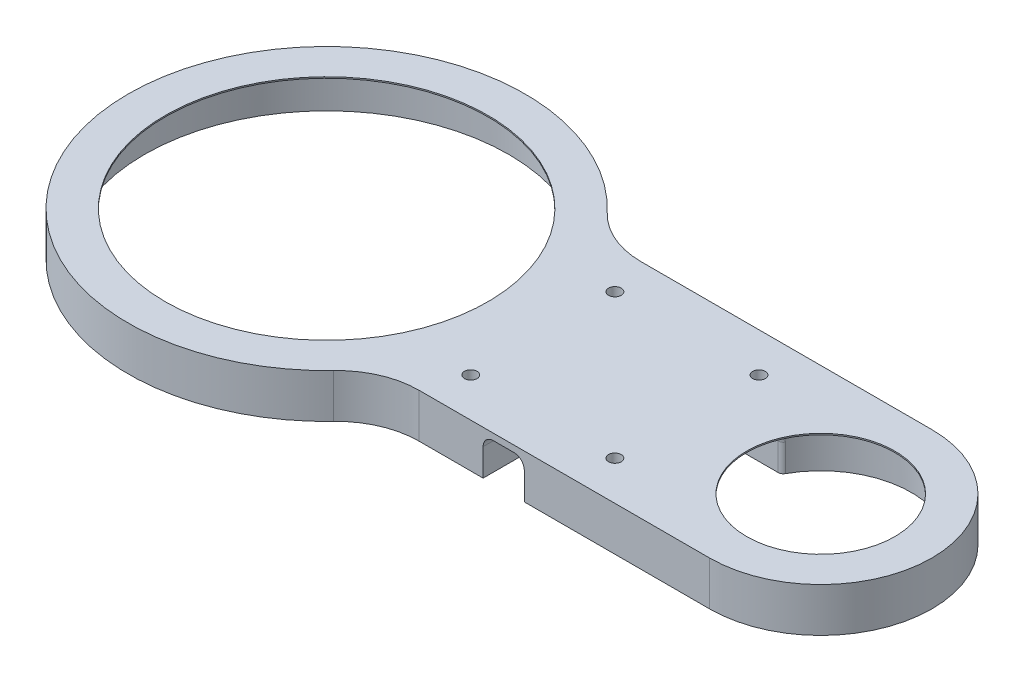
SolidWorks part; units mm, degrees
ref_plane "Front Plane" through (0, 0, 0) normal (0, 0, 1) x (1, 0, 0)
ref_plane "Top Plane" through (0, 0, 0) normal (0, 1, 0) x (1, 0, 0)
ref_plane "Right Plane" through (0, 0, 0) normal (1, 0, 0) x (0, 0, -1)
sketch "Sketch1" plane through (0, 0, 0) normal (0, 1, 0) x (1, 0, 0)
  line L0 (0, 0) -> (76.2, 0) construction
  line L1 (25.3542, -17.145) -> (76.2, -17.145)
  line L2 (25.3542, 17.145) -> (76.2, 17.145)
  circle A0 centre (0, 0) radius 28.067
  circle A1 centre (76.2, 0) radius 13.97
  arc A2 (76.2, 17.145) -> (76.2, -17.145) centre (76.2, 0) cw
  arc A3 (25.3542, 17.145) -> (25.3542, -17.145) centre (0, 0) ccw
  dimension "D1" = 56.134
  dimension "D2" = 27.94
  dimension "D4" = 3.175
  dimension "D5" = 2.54
  dimension "D3" = 76.2
extrude "Boss-Extrude1" add sketch "Sketch1" along normal blind 6.6
fillet "Fillet1" radius 12.7 2 edges at (25.3542, 3.3, -17.145) (25.3542, 3.3, 17.145)
sketch "Sketch2" plane through (0, 6.6, 0) normal (0, 1, 0) x (1, 0, 0)
  line L2 (76.2, 17.145) -> (31.3811, 17.145)
  line L3 (31.3811, -17.145) -> (76.2, -17.145)
  line L4 (76.2, 17.145) -> (31.3811, 17.145)
  line L5 (31.3811, -17.145) -> (76.2, -17.145)
  circle A0 centre (0, 0) radius 24.892
  circle A1 centre (0, 0) radius 28.067 construction
  circle A3 centre (76.2, 0) radius 13.97 construction
  arc A4 (76.2, -17.145) -> (76.2, 17.145) centre (76.2, 0) ccw
  arc A5 (22.1784, 21.0928) -> (31.3811, 17.145) centre (31.3811, 29.845) ccw
  arc A6 (22.1784, 21.0928) -> (22.1784, -21.0928) centre (0, 0) ccw
  arc A7 (31.3811, -17.145) -> (22.1784, -21.0928) centre (31.3811, -29.845) ccw
  arc A8 (76.2, -17.145) -> (76.2, 17.145) centre (76.2, 0) ccw
  arc A9 (22.1784, 21.0928) -> (31.3811, 17.145) centre (31.3811, 29.845) ccw
  arc A10 (22.1784, 21.0928) -> (22.1784, -21.0928) centre (0, 0) ccw
  arc A11 (31.3811, -17.145) -> (22.1784, -21.0928) centre (31.3811, -29.845) ccw
  circle A13 centre (76.2, 0) radius 11.43
  dimension "D2" = 3.175
  dimension "D3" = 2.54
  dimension "D1" = 0
extrude "Boss-Extrude2" add sketch "Sketch2" along normal blind 0.2
fillet "Fillet2" radius 0.7937 2 edges at (76.2, 6.6, 13.97) (0, 6.6, 28.067)
sketch "Sketch6" plane through (0, 0, 0) normal (0, -1, 0) x (1, 0, 0)
  line L0 (31.3811, 17.145) -> (76.2, 17.145) construction
  line L1 (76.2, 6.35) -> (47.625, 6.35)
  line L2 (76.2, 6.35) -> (76.2, -6.35)
  line L3 (76.2, -6.35) -> (0, -6.35)
  line L4 (0, 6.35) -> (0, -6.35)
  line L5 (47.625, 6.35) -> (41.275, 6.35) construction
  line L6 (47.625, 6.35) -> (47.625, 17.145)
  line L7 (47.625, 17.145) -> (41.275, 17.145)
  line L8 (41.275, 6.35) -> (41.275, 17.145)
  line L9 (47.625, 6.35) -> (41.275, 6.35) construction
  line L10 (41.275, 6.35) -> (0, 6.35)
  circle A1 centre (76.2, 0) radius 13.97 construction
  point P4 (76.2, 0)
  point P7 (0, 0)
  point P13 (44.45, 17.145)
  dimension "D1" = 12.7
  dimension "D2" = 31.75
  dimension "D3" = 6.35
extrude "Cut-Extrude4" cut sketch "Sketch6" against normal offset from surface (5.8 mm away) 1 up to face at (0, 6.8, 24.892)
fillet "Fillet3" radius 3.175 2 edges at (41.275, 2.9, 6.35) (47.625, 2.9, 6.35)
fillet "Fillet4" radius 1.5875 7 edges at (57.2783, 5.8, 6.35) (47.625, 5.8, 13.335) (32.7196, 5.8, 6.35) (40.3451, 5.8, 7.2799) (48.5549, 5.8, 7.2799) (41.275, 5.8, 13.335) (45.5479, 5.8, -6.35)
fillet "Fillet5" radius 0.7937 10 edges at (27.3392, 2.1062, 6.35) (27.4681, 5.4415, 5.7673) (28.067, 5.8, 0) (27.4146, 5.1861, -6.0164) (63.7566, 2.1062, 6.35) (63.6123, 5.1287, 6.0589) (62.23, 5.8, 0) (63.4959, 5.4045, -5.8109) (27.3392, 2.1062, -6.35) (63.7566, 2.1062, -6.35)
sketch "Sketch7" plane through (0, 0, 0) normal (0, -1, 0) x (1, 0, 0)
  line L0 (93.345, 0) -> (90.17, 0) construction
  arc A0 (76.2, -17.145) -> (76.2, 17.145) centre (76.2, 0) ccw construction
  arc A1 (63.6716, -6.1806) -> (63.6716, 6.1806) centre (76.2, 0) ccw construction
  circle A2 centre (91.7575, 0) radius 0.7
  point P10 (76.2, 0)
  dimension "D1" = 1.4
extrude "Cut-Extrude5" cut sketch "Sketch7" against normal blind 4
pattern_circular "CirPattern1" count 12 over 360 about axis through (76.2, 6.6, 0) along (0, -1, 0) skipping 4, 5, 6, 7, 8 of "Cut-Extrude5" reverse direction yes
sketch "Sketch8" plane through (0, 0, 0) normal (0, -1, 0) x (1, 0, 0)
  line L0 (-28.067, 0) -> (-30.607, 0) construction
  arc A0 (27.1936, 6.9473) -> (27.1936, -6.9473) centre (0, 0) ccw construction
  arc A1 (22.1784, 21.0928) -> (22.1784, -21.0928) centre (0, 0) ccw construction
  circle A2 centre (-29.337, 0) radius 0.7
  dimension "D1" = 1.4
extrude "Cut-Extrude6" cut sketch "Sketch8" against normal blind 4
pattern_circular "CirPattern2" count 12 over 360 about axis through (0, 6.6, 0) along (0, -1, 0) skipping 6 of "Cut-Extrude6"
sketch "Sketch9" plane through (0, 0, 0) normal (0, -1, 0) x (1, 0, 0)
  line L0 (66.675, 15.5575) -> (53.975, 15.5575) construction
  line L1 (53.975, 15.5575) -> (34.925, 15.5575) construction
  line L2 (46.0375, 17.145) -> (42.8625, 17.145) construction
  line L3 (44.45, 15.5575) -> (44.45, 17.145) construction
  line L4 (76.2, 15.5575) -> (66.675, 15.5575) construction
  circle A0 centre (66.675, 15.5575) radius 0.7
  circle A1 centre (53.975, 15.5575) radius 0.7
  circle A2 centre (34.925, 15.5575) radius 0.7
  circle A3 centre (76.2, 15.5575) radius 0.7 construction
  point P14 (44.45, 15.5575)
  dimension "D1" = 19.05
  dimension "D2" = 12.7
extrude "Cut-Extrude7" cut sketch "Sketch9" against normal blind 4
mirror "Mirror1" about plane through (0, 0, 0) normal (0, 0, 1) of "Cut-Extrude7"
sketch "Sketch10" plane through (0, 0, 0) normal (0, -1, 0) x (1, 0, 0)
  line L0 (46.0375, 17.145) -> (42.8625, 17.145) construction
  line L1 (55.5625, -11.1125) -> (33.3375, -11.1125) construction
  line L2 (55.5625, -11.1125) -> (55.5625, 11.1125) construction
  line L3 (55.5625, 11.1125) -> (33.3375, 11.1125) construction
  line L4 (33.3375, -11.1125) -> (33.3375, 11.1125) construction
  line L5 (55.5625, -11.1125) -> (33.3375, 11.1125) construction
  line L6 (55.5625, 11.1125) -> (33.3375, -11.1125) construction
  circle A0 centre (33.3375, 11.1125) radius 0.975
  circle A1 centre (55.5625, 11.1125) radius 0.975
  circle A2 centre (55.5625, -11.1125) radius 0.975
  circle A3 centre (33.3375, -11.1125) radius 0.975
  point P0 (44.45, 0)
  point P11 (44.45, 17.145)
  dimension "D2" = 1.95
  dimension "D1" = 22.225
extrude "Cut-Extrude8" cut sketch "Sketch10" against normal through all
